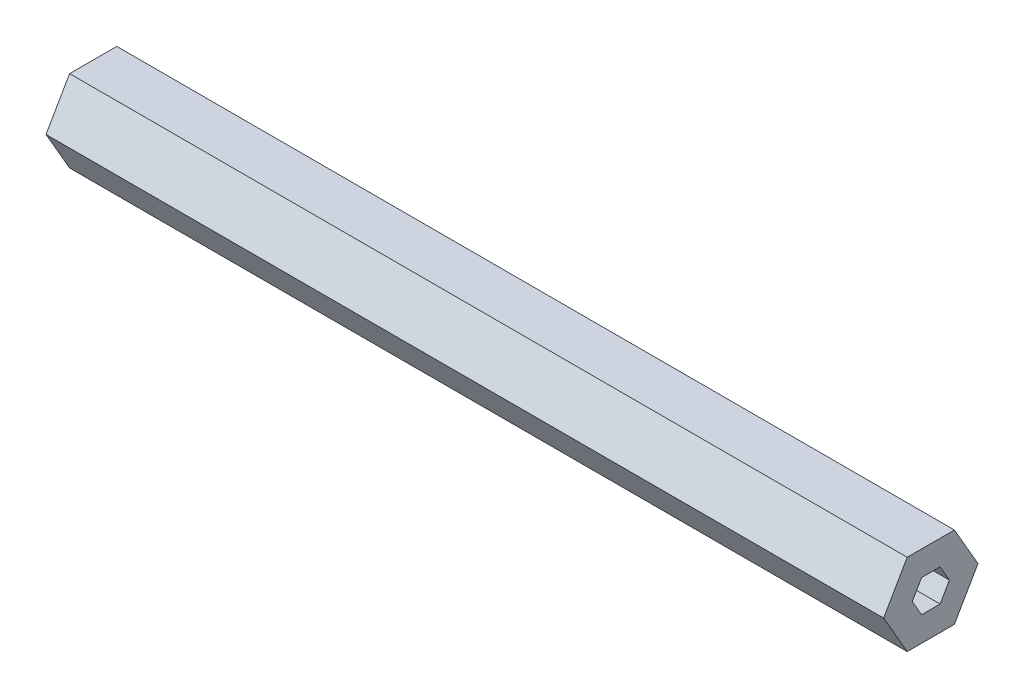
SolidWorks part; units mm, degrees
material "6061-T6 (SS)"
ref_plane "Front" through (0, 0, 0) normal (0, 0, 1) x (1, 0, 0)
ref_plane "Top" through (0, 0, 0) normal (0, 1, 0) x (1, 0, 0)
ref_plane "Right" through (0, 0, 0) normal (1, 0, 0) x (0, 0, -1)
sketch "Sketch1" plane through (0, 0, 0) normal (1, 0, 0) x (0, 0, -1)
  line L1 (7.3323, 0) -> (3.6662, 6.35)
  line L2 (3.6662, 6.35) -> (-3.6662, 6.35)
  line L3 (-3.6662, 6.35) -> (-7.3323, 0)
  line L4 (-7.3323, 0) -> (-3.6662, -6.35)
  line L5 (-3.6662, -6.35) -> (3.6662, -6.35)
  line L6 (3.6662, -6.35) -> (7.3323, 0)
  line L7 (2.8868, 0) -> (1.4434, 2.5)
  line L8 (1.4434, 2.5) -> (-1.4434, 2.5)
  line L9 (-1.4434, 2.5) -> (-2.8868, 0)
  line L10 (-2.8868, 0) -> (-1.4434, -2.5)
  line L11 (-1.4434, -2.5) -> (1.4434, -2.5)
  line L12 (1.4434, -2.5) -> (2.8868, 0)
  circle A0 centre (0, 0) radius 6.35 construction
  circle A1 centre (0, 0) radius 2.5 construction
  dimension "D1" = 12.7
  dimension "D2" = 5
extrude "Boss-Extrude1" add sketch "Sketch1" along normal blind 130.175
ref_axis "Axis1" through (-80.9, 0, 0) along (1, 0, 0)
